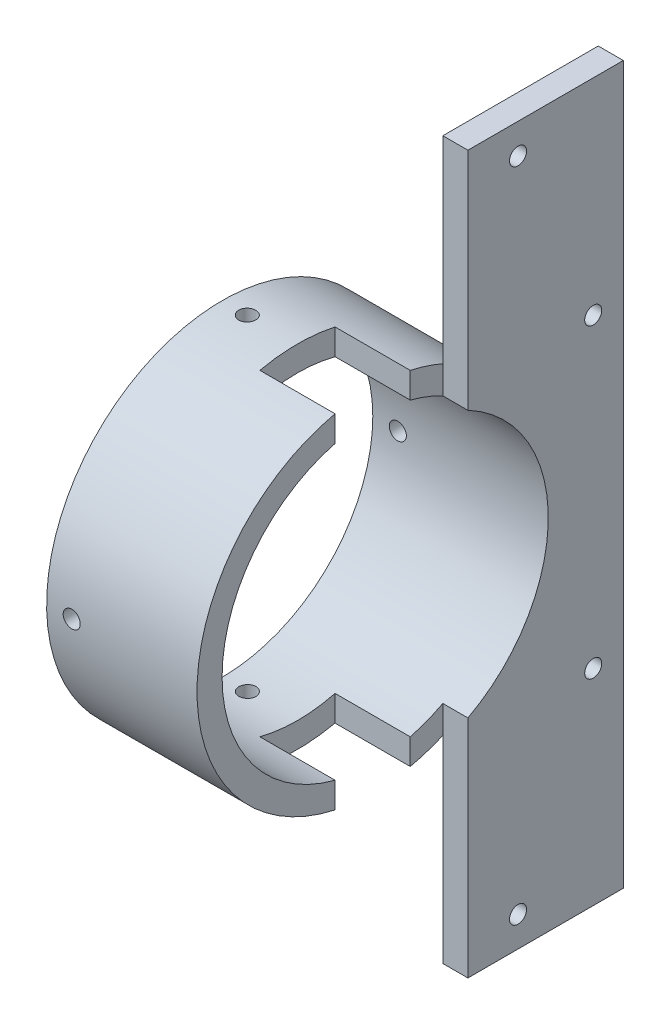
SolidWorks part; units mm, degrees
ref_plane "Front Plane" through (0, 0, 0) normal (0, 0, 1) x (1, 0, 0)
ref_plane "Top Plane" through (0, 0, 0) normal (0, 1, 0) x (1, 0, 0)
ref_plane "Right Plane" through (0, 0, 0) normal (1, 0, 0) x (0, 0, -1)
sketch "Sketch1" plane through (0, 0, 0) normal (1, 0, 0) x (0, 0, -1)
  circle A0 centre (0, 0) radius 30.0312
  circle A1 centre (0, 0) radius 35.0312
  dimension "D1" = 60.0625
  dimension "D2" = 5
extrude "Boss-Extrude1" add sketch "Sketch1" along normal blind 30
ref_plane "Plane1" through (0, 35.0312, 0) normal (0, 1, 0) x (1, 0, 0)
sketch "Sketch4" plane through (0, 35.0312, 0) normal (0, 1, 0) x (1, 0, 0)
  point P0 (5, 0)
  dimension "D1" = 5
hole_wizard "M3 Clearance Hole2" positions "Sketch4" profile "Sketch5" hole size "M3" standard "ANSI Metric" end condition through all
sketch "Sketch5" plane through (5, 35.0312, 0) normal (1, 0, 0) x (0, 0, 1)
  line L0 (0, 0) -> (0, 70.0625)
  line L1 (0, 70.0625) -> (1.7, 70.0625)
  line L2 (1.7, 70.0625) -> (1.7, 0)
  line L5 (1.7, 0) -> (0, 0)
  line L11 (0, -6.35) -> (0, 107.95) construction
  dimension "Thru Hole Dia." = 3.4
  dimension "Thru Hole Depth" = 70.0625
ref_plane "Plane2" through (0, 0, 35.0312) normal (0, 0, 1) x (1, 0, 0)
sketch "Sketch6" plane through (0, 0, 35.0312) normal (0, 0, 1) x (1, 0, 0)
  point P0 (5, 0)
  dimension "D1" = 5
hole_wizard "M3 Clearance Hole3" positions "Sketch6" profile "Sketch7" hole size "M3" standard "ANSI Metric" end condition through all
sketch "Sketch7" plane through (5, 0, 35.0312) normal (1, 0, 0) x (0, -1, 0)
  line L0 (0, 0) -> (0, 70.0625)
  line L1 (0, 70.0625) -> (1.7, 70.0625)
  line L2 (1.7, 70.0625) -> (1.7, 0)
  line L5 (1.7, 0) -> (0, 0)
  line L11 (0, -6.35) -> (0, 107.95) construction
  dimension "Thru Hole Dia." = 3.4
  dimension "Thru Hole Depth" = 70.0625
sketch "Sketch9" plane through (30, 0, 0) normal (1, 0, 0) x (0, 0, -1)
  line L0 (0, 0) -> (-14.9677, 0) construction
  line L1 (14, 71.5) -> (45, 71.5)
  line L2 (14, 71.5) -> (14, 26.5683)
  line L3 (14, -71.5) -> (45, -71.5)
  line L4 (45, 71.5) -> (45, -71.5)
  line L5 (-5, 74) -> (5, 74) construction
  line L6 (-5, 74) -> (-5, 19) construction
  line L7 (-5, 19) -> (5, 19) construction
  line L8 (5, 74) -> (5, 19) construction
  line L9 (5, -74) -> (5, -19) construction
  line L10 (-5, -19) -> (5, -19) construction
  line L11 (-5, -74) -> (-5, -19) construction
  line L12 (-5, -74) -> (5, -74) construction
  line L14 (14, -26.5683) -> (14, -71.5)
  line L15 (-4, 46.5) -> (14, 46.5) construction
  circle A0 centre (0, 0) radius 30.0312 construction
  arc A1 (14, -26.5683) -> (14, 26.5683) centre (0, 0) ccw
  point P11 (5, 46.5)
  point P17 (5, -46.5)
  point P19 (0, 0)
  point P20 (51.4918, 28.1389)
  point P22 (0, 74)
  point P24 (59.6759, 66.5)
  point P25 (45, 0)
  point P26 (51.8378, 66.5)
  point P27 (46, 57.9917)
  point P28 (0, 0)
  point P29 (0, 0)
  point P30 (0, 0)
  point P31 (8.5478, 71.5)
  dimension "D1" = 55
  dimension "D2" = 38
  dimension "D3" = 10
  dimension "D4" = 18
  dimension "D7" = 1
  dimension "D8" = 25
  dimension "D9" = 45
extrude "Boss-Extrude2" add sketch "Sketch9" along normal blind 5
sketch "Sketch11" plane through (35, 0, 0) normal (1, 0, 0) x (0, 0, -1)
  line L1 (1, 47.3937) -> (10, 47.3937)
  line L2 (1, 47.3937) -> (1, 39.1813)
  line L3 (1, 39.1813) -> (10, 39.1813)
  line L4 (10, 47.3937) -> (10, 39.1813)
  line L5 (10, 33.7924) -> (39, 33.7924)
  line L6 (10, 33.7924) -> (10, 51.1979)
  line L7 (10, 51.1979) -> (39, 51.1979)
  line L8 (39, 33.7924) -> (39, 51.1979)
  line L9 (34, 54.1979) -> (14, 54.1979)
  line L10 (34, 54.1979) -> (34, 31.3507)
  line L11 (34, 31.3507) -> (14, 31.3507)
  line L12 (14, 54.1979) -> (14, 31.3507)
  point P15 (44.982, 56.0314)
  point P21 (39, 59.1979)
  dimension "D1" = 1
  dimension "D2" = 9
  dimension "D3" = 38
  dimension "D4" = 20
  dimension "D5" = 5
  dimension "D6" = 3
  dimension "D7" = 5
  dimension "D8" = 5
sketch "Sketch12" plane through (35, 0, 0) normal (1, 0, 0) x (0, 0, -1)
  line L2 (0, 0) -> (12.8828, 0) construction
  point P1 (39, 30.5)
  point P14 (24, 65.5)
  point P24 (24, -65.5)
  point P25 (39, -30.5)
  dimension "D1" = 34
  dimension "D2" = 16
  dimension "D3" = 35
  dimension "D4" = 19
hole_wizard "M3 Clearance Hole4" positions "Sketch12" profile "Sketch13" hole size "M3" standard "ANSI Metric" end condition through all
sketch "Sketch13" plane through (35, 30.5, -39) normal (0, 1, 0) x (0, 0, -1)
  line L0 (0, 0) -> (0, 35)
  line L1 (0, 35) -> (1.7, 35)
  line L2 (1.7, 35) -> (1.7, 0)
  line L5 (1.7, 0) -> (0, 0)
  line L11 (0, -6.35) -> (0, 107.95) construction
  dimension "Thru Hole Dia." = 3.4
  dimension "Thru Hole Depth" = 35
sketch "Sketch14" plane through (30, 0, 0) normal (1, 0, 0) x (0, 0, -1)
  line L1 (-7.5, 77.0088) -> (7.5, 77.0088)
  line L2 (-7.5, 77.0088) -> (-7.5, -46.9193)
  line L3 (-7.5, -46.9193) -> (7.5, -46.9193)
  line L4 (7.5, 77.0088) -> (7.5, -46.9193)
  point P4 (0, 77.0088)
  point P6 (-7.5, -46.9193)
  point P7 (-7.5, 77.0088)
  dimension "D1" = 15
  dimension "D2" = 46.9193
  dimension "D3" = 123.9281
extrude "Cut-Extrude1" cut sketch "Sketch14" against normal blind 15
